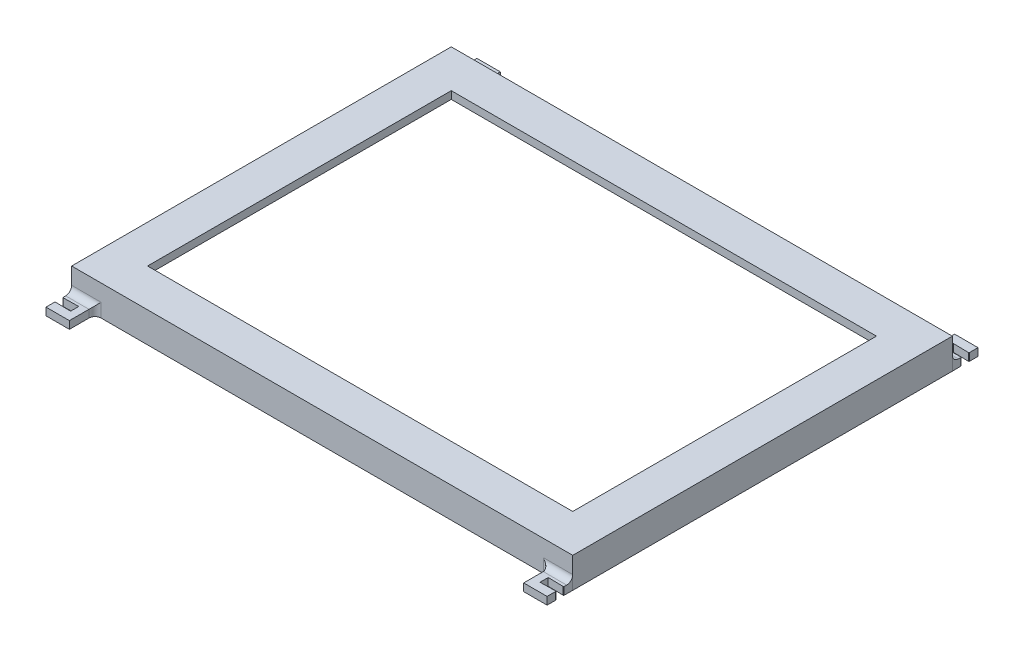
SolidWorks part; units mm, degrees
ref_plane "Front Plane" through (0, 0, 0) normal (0, 0, 1) x (1, 0, 0)
ref_plane "Top Plane" through (0, 0, 0) normal (0, 1, 0) x (1, 0, 0)
ref_plane "Right Plane" through (0, 0, 0) normal (1, 0, 0) x (0, 0, -1)
sketch "Sketch1" plane through (0, 9.525, 0) normal (0, 1, 0) x (1, 0, 0)
  line L12 (261.9455, 40.3596) -> (84.1455, 40.3596)
  line L13 (84.1455, 40.3596) -> (84.1455, -86.6404)
  line L14 (84.1455, -86.6404) -> (261.9455, -86.6404)
  line L15 (261.9455, -86.6404) -> (261.9455, 40.3596)
  line L16 (277.8205, 56.2346) -> (68.2705, 56.2346)
  line L17 (277.8205, -102.5154) -> (277.8205, 56.2346)
  line L18 (68.2705, -102.5154) -> (277.8205, -102.5154)
  line L19 (68.2705, 56.2346) -> (68.2705, -102.5154)
  line L20 (277.8205, 56.2346) -> (68.2705, 56.2346)
  line L21 (277.8205, -102.5154) -> (277.8205, 56.2346)
  line L22 (68.2705, -102.5154) -> (277.8205, -102.5154)
  line L23 (68.2705, 56.2346) -> (68.2705, -102.5154)
  dimension "D1" = 3.175
extrude "FrontFace" add sketch "Sketch1" along normal blind 3.175
sketch "Sketch3" plane through (0, 9.525, 0) normal (0, -1, 0) x (1, 0, 0)
  line L4 (277.8205, -56.2346) -> (277.8205, 102.5154)
  line L5 (277.8205, 102.5154) -> (68.2705, 102.5154)
  line L6 (68.2705, 102.5154) -> (68.2705, -56.2346)
  line L7 (68.2705, -56.2346) -> (277.8205, -56.2346)
  line L8 (277.8205, -56.2346) -> (277.8205, 102.5154)
  line L9 (277.8205, 102.5154) -> (68.2705, 102.5154)
  line L10 (68.2705, 102.5154) -> (68.2705, -56.2346)
  line L11 (68.2705, -56.2346) -> (277.8205, -56.2346)
  line L12 (71.1915, 99.5944) -> (71.1915, -53.3136)
  line L17 (71.1915, -53.3136) -> (274.8995, -53.3136)
  line L18 (274.8995, 99.5944) -> (274.8995, -53.3136)
  line L19 (71.1915, 99.5944) -> (274.8995, 99.5944)
  dimension "D1" = 0
extrude "SideShell" add sketch "Sketch3" along normal up to surface (9.525 mm away)
sketch "Sketch9" plane through (0, 0, 0) normal (0, -1, 0) x (1, 0, 0)
  line L0 (277.8205, 102.5154) -> (268.0366, 102.5154)
  line L1 (68.2705, 102.5154) -> (277.8205, 102.5154) construction
  line L2 (268.0366, 102.5154) -> (268.0366, 113.2376)
  line L3 (268.0366, 113.2376) -> (277.8205, 113.2376)
  line L4 (277.8205, 113.2376) -> (277.8205, 109.7211)
  line L5 (277.5616, 109.4672) -> (271.2116, 109.591)
  line L6 (271.2116, 109.591) -> (271.2116, 106.162)
  line L7 (271.2116, 106.162) -> (277.5204, 106.2826)
  line L8 (277.7792, 106.0316) -> (277.8205, 102.5154)
  line L9 (173.0455, 102.5154) -> (173.0455, -56.2346) construction
  line L12 (277.8205, -56.2346) -> (68.2705, -56.2346) construction
  line L39 (68.2705, 23.1404) -> (277.8205, 23.1404) construction
  line L40 (68.2705, -56.2346) -> (68.2705, 102.5154) construction
  line L41 (277.8205, 102.5154) -> (277.8205, -56.2346) construction
  line L42 (277.7792, -59.7509) -> (277.8205, -56.2346)
  line L43 (271.2116, -59.8812) -> (277.5204, -60.0018)
  line L44 (271.2116, -63.3102) -> (271.2116, -59.8812)
  line L45 (277.5616, -63.1865) -> (271.2116, -63.3102)
  line L46 (277.8205, -66.9569) -> (277.8205, -63.4404)
  line L47 (268.0366, -66.9569) -> (277.8205, -66.9569)
  line L48 (268.0366, -56.2346) -> (268.0366, -66.9569)
  line L49 (277.8205, -56.2346) -> (268.0366, -56.2346)
  line L50 (68.2705, -56.2346) -> (78.0545, -56.2346)
  line L51 (78.0545, -56.2346) -> (78.0545, -66.9569)
  line L52 (78.0545, -66.9569) -> (68.2705, -66.9569)
  line L53 (68.2705, -66.9569) -> (68.2705, -63.4404)
  line L54 (68.5295, -63.1865) -> (74.8795, -63.3102)
  line L55 (74.8795, -63.3102) -> (74.8795, -59.8812)
  line L56 (74.8795, -59.8812) -> (68.5707, -60.0018)
  line L57 (68.3118, -59.7509) -> (68.2705, -56.2346)
  line L58 (68.3118, 106.0316) -> (68.2705, 102.5154)
  line L59 (74.8795, 106.162) -> (68.5707, 106.2826)
  line L60 (74.8795, 109.591) -> (74.8795, 106.162)
  line L61 (68.5295, 109.4672) -> (74.8795, 109.591)
  line L62 (68.2705, 113.2376) -> (68.2705, 109.7211)
  line L63 (78.0545, 113.2376) -> (68.2705, 113.2376)
  line L64 (78.0545, 102.5154) -> (78.0545, 113.2376)
  line L65 (68.2705, 102.5154) -> (78.0545, 102.5154)
  arc A0 (277.5204, 106.2826) -> (277.7792, 106.0316) centre (277.5252, 106.0286) cw
  arc A1 (277.8205, 109.7211) -> (277.5616, 109.4672) centre (277.5665, 109.7211) cw
  arc A8 (277.8205, -63.4404) -> (277.5616, -63.1865) centre (277.5665, -63.4404) ccw
  arc A9 (277.5204, -60.0018) -> (277.7792, -59.7509) centre (277.5252, -59.7479) ccw
  arc A10 (68.5707, -60.0018) -> (68.3118, -59.7509) centre (68.5658, -59.7479) cw
  arc A11 (68.2705, -63.4404) -> (68.5295, -63.1865) centre (68.5245, -63.4404) cw
  arc A12 (68.2705, 109.7211) -> (68.5295, 109.4672) centre (68.5245, 109.7211) ccw
  arc A13 (68.5707, 106.2826) -> (68.3118, 106.0316) centre (68.5658, 106.0286) ccw
  point P14 (277.7762, 106.2875)
  point P17 (277.8205, 109.4621)
  point P18 (271.2116, 107.8765)
  point P19 (268.0366, 107.8765)
  point P41 (277.8205, -63.1814)
  point P42 (277.7762, -60.0067)
  point P67 (68.3149, -60.0067)
  point P68 (68.2705, -63.1814)
  point P69 (68.2705, 109.4621)
  point P70 (68.3149, 106.2875)
  dimension "D3" = 0.254
  dimension "D1" = 3.175
  dimension "D2" = 3.429
  dimension "D4" = 6.35
  dimension "D5" = 3.175
extrude "BottomSupportLock" add sketch "Sketch9" against normal blind 3.175
fillet "Fillet1" radius 2.54 8 edges at (268.0366, 1.5875, 102.5154) (272.9285, 3.175, 102.5154) (268.0366, 1.5875, -56.2346) (272.9285, 3.175, -56.2346) (78.0545, 1.5875, -56.2346) (73.1625, 3.175, -56.2346) (78.0545, 1.5875, 102.5154) (73.1625, 3.175, 102.5154)
